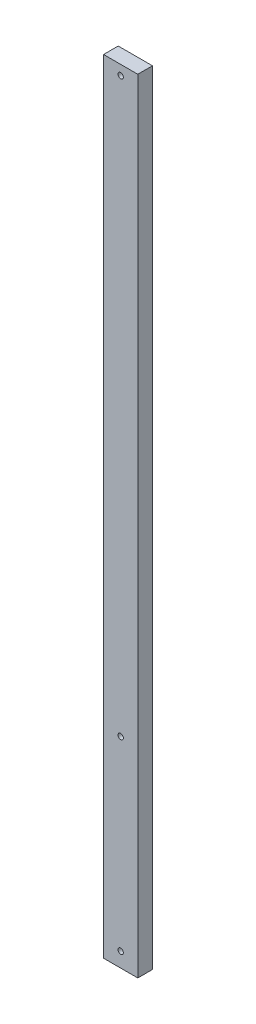
SolidWorks part; units mm, degrees
material "Oak"
ref_plane "Front Plane" through (0, 0, 0) normal (0, 0, 1) x (1, 0, 0)
ref_plane "Top Plane" through (0, 0, 0) normal (0, 1, 0) x (1, 0, 0)
ref_plane "Right Plane" through (0, 0, 0) normal (1, 0, 0) x (0, 0, -1)
sketch "Sketch1" plane through (0, 0, 0) normal (0, 1, 0) x (1, 0, 0)
  line L1 (-44.45, -19.05) -> (44.45, -19.05)
  line L2 (-44.45, -19.05) -> (-44.45, 19.05)
  line L3 (-44.45, 19.05) -> (44.45, 19.05)
  line L4 (44.45, -19.05) -> (44.45, 19.05)
  line L5 (-44.45, -19.05) -> (44.45, 19.05) construction
  line L6 (-44.45, 19.05) -> (44.45, -19.05) construction
  point P0 (0, 0)
  dimension "D1" = 38.1
  dimension "D2" = 88.9
extrude "Boss-Extrude1" add sketch "Sketch1" along normal blind 2032 contours L3 L4 L1 L2
sketch "Sketch2" plane through (0, 0, 19.05) normal (0, 0, 1) x (1, 0, 0)
  line L0 (0, 2032) -> (0, 0) construction
  line L1 (-44.45, 2032) -> (44.45, 2032) construction
  line L2 (-44.45, 0) -> (44.45, 0) construction
  circle A0 centre (0, 38.1) radius 6.985
  circle A1 centre (0, 520.7) radius 6.985
  circle A2 centre (0, 2006.6) radius 6.985
  dimension "D1" = 13.97
  dimension "D2" = 38.1
  dimension "D3" = 520.7
  dimension "D4" = 2006.6
extrude "Cut-Extrude1" cut sketch "Sketch2" against normal through all both and the other way through all
